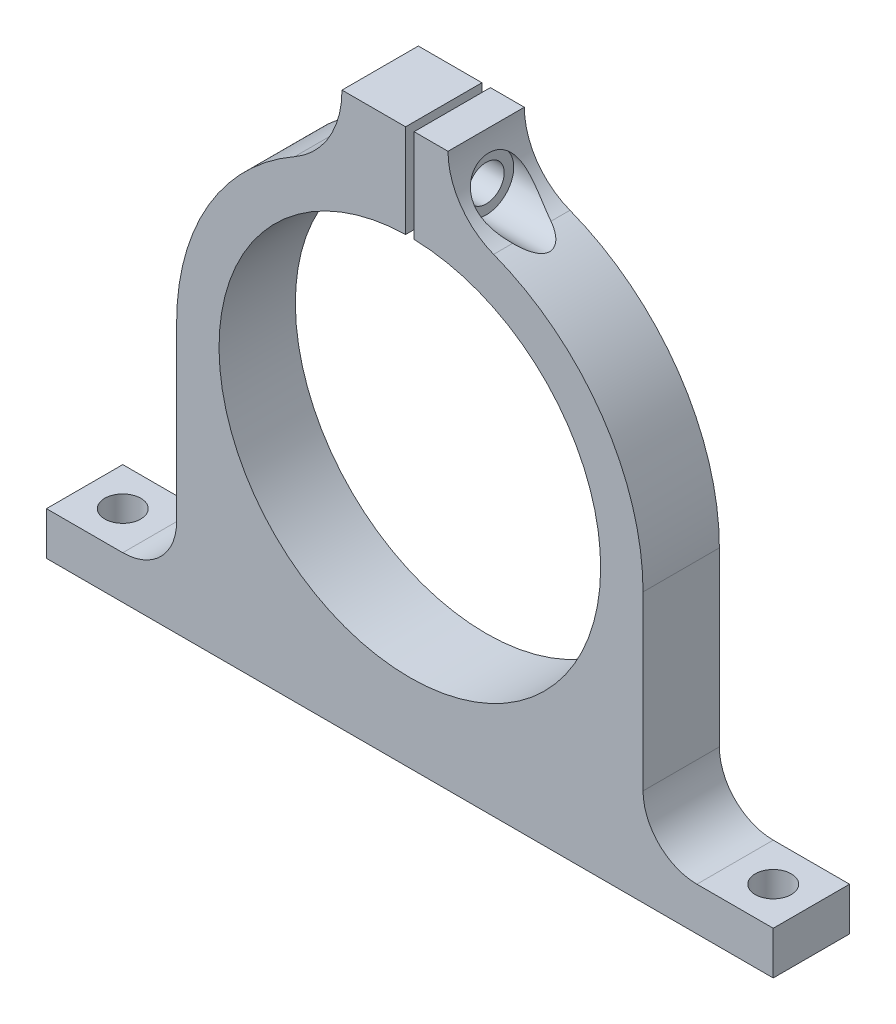
SolidWorks part; units mm, degrees
ref_plane "Front Plane" through (0, 0, 0) normal (0, 0, 1) x (1, 0, 0)
ref_plane "Top Plane" through (0, 0, 0) normal (0, 1, 0) x (1, 0, 0)
ref_plane "Right Plane" through (0, 0, 0) normal (1, 0, 0) x (0, 0, -1)
sketch "Sketch1" plane through (0, 0, 0) normal (0, 0, 1) x (1, 0, 0)
  line L0 (0, 0) -> (0, 55) construction
  line L1 (0, 0) -> (85.7, 0) construction
  line L2 (0, 0) -> (-85.7, 0) construction
  line L3 (85.7, -53.34) -> (85.7, -63.5)
  line L4 (85.7, -63.5) -> (-85.7, -63.5)
  line L5 (-85.7, -63.5) -> (-85.7, -53.34)
  line L6 (0, 55) -> (0, 67) construction
  line L7 (0, 67) -> (1, 67) construction
  line L8 (1, 67) -> (1, 44.9889)
  line L9 (1, 67) -> (9, 67)
  line L10 (-45, 0) -> (-55, 0) construction
  line L11 (0, 67) -> (-1, 67) construction
  line L12 (-1, 67) -> (-1, 44.9889)
  line L13 (-1, 67) -> (-16, 67)
  line L14 (-55, 0) -> (-55, -40.64)
  line L15 (-67.7, -53.34) -> (-85.7, -53.34)
  line L16 (55, 0) -> (55, -40.64)
  line L17 (67.7, -53.34) -> (85.7, -53.34)
  arc A0 (-1, 44.9889) -> (1, 44.9889) centre (0, 0) ccw
  arc A1 (55, 0) -> (19.76, 51.3278) centre (0, 0) ccw
  arc A2 (-27.1614, 47.8253) -> (-55, 0) centre (0, 0) ccw
  arc A3 (9, 67) -> (19.76, 51.3278) centre (25.7935, 67) ccw
  arc A4 (55, -40.64) -> (67.7, -53.34) centre (67.7, -40.64) ccw
  arc A5 (-55, -40.64) -> (-67.7, -53.34) centre (-67.7, -40.64) cw
  arc A6 (-27.1614, 47.8253) -> (-16, 67) centre (-38.0513, 67) ccw
  dimension "D1" = 90
  dimension "D3" = 12.7
  dimension "D4" = 18
  dimension "D2" = 10
  dimension "D5" = 10.16
  dimension "D6" = 12
  dimension "D7" = 1
  dimension "D8" = 8
  dimension "D9" = 1
  dimension "D10" = 15
  dimension "D11" = 63.5
extrude "main body" add sketch "Sketch1" along normal blind 18
sketch "Sketch7" plane through (1, 0, 0) normal (-1, 0, 0) x (0, 0, 1)
  line L0 (9, 44.9889) -> (9, 67) construction
  line L1 (18, 44.9889) -> (0, 44.9889) construction
  line L2 (18, 67) -> (0, 67) construction
  circle A0 centre (9, 55.9944) radius 3.5
  dimension "D1" = 7
extrude "clamp tap" cut sketch "Sketch7" against normal through all and the other way through all
ref_plane "Plane2" through (-16, 0, 0) normal (1, 0, 0) x (0, 0, -1)
sketch "Sketch8" plane through (-16, 0, 0) normal (1, 0, 0) x (0, 0, -1)
  circle A0 centre (-9, 55.9944) radius 6.5
  dimension "D1" = 13
ref_plane "Plane3" through (9, 0, 0) normal (-1, 0, 0) x (0, 0, 1)
sketch "Sketch10" plane through (9, 0, 0) normal (-1, 0, 0) x (0, 0, 1)
  circle A0 centre (9, 55.9944) radius 6.5
  dimension "D1" = 13
extrude "head counterbore" cut sketch "Sketch10" against normal blind 18
sketch "Sketch11" plane through (0, -53.34, 0) normal (0, 1, 0) x (1, 0, 0)
  line L0 (-76.7, 0) -> (-76.7, -18) construction
  line L1 (-67.7, 0) -> (-85.7, 0) construction
  line L2 (-67.7, -18) -> (-85.7, -18) construction
  line L3 (76.7, 0) -> (76.7, -18) construction
  line L4 (85.7, 0) -> (67.7, 0) construction
  line L5 (85.7, -18) -> (67.7, -18) construction
  circle A0 centre (-76.7, -9) radius 4.25
  circle A1 centre (76.7, -9) radius 4.25
  dimension "D1" = 8.5
extrude "mount bolts" cut sketch "Sketch11" against normal through all
sketch "Sketch12" plane through (9, 0, 0) normal (-1, 0, 0) x (0, 0, 1)
  circle A0 centre (9, 55.9944) radius 4.25
  dimension "D1" = 8.5
extrude "clamp m8 clearance" cut sketch "Sketch12" along normal up to surface (8 mm away) up to face at (1, 59.4944, 9)
